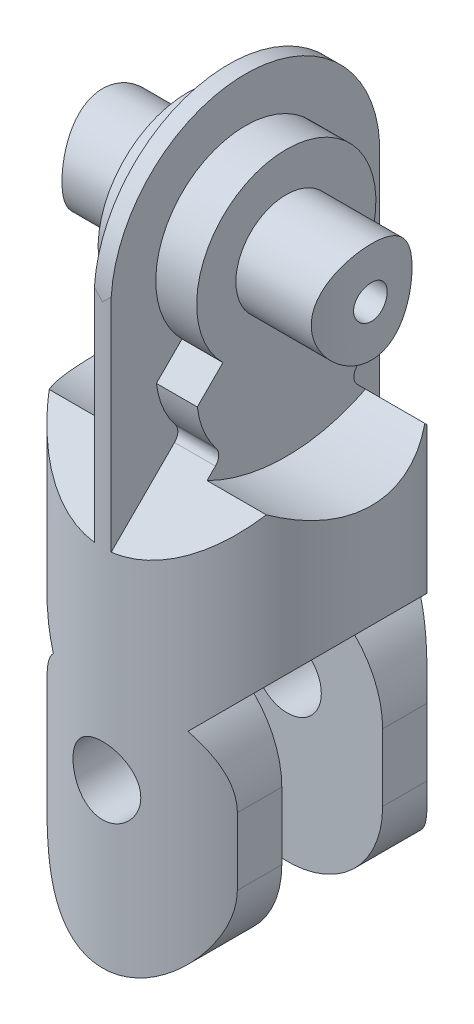
SolidWorks part; units mm, degrees
ref_plane "Front Plane" through (0, 0, 0) normal (0, 0, 1) x (1, 0, 0)
ref_plane "Top Plane" through (0, 0, 0) normal (0, 1, 0) x (1, 0, 0)
ref_plane "Right Plane" through (0, 0, 0) normal (1, 0, 0) x (0, 0, -1)
sketch "Sketch2" plane through (0, 0, 0) normal (0, 0, 1) x (1, 0, 0)
  line L0 (0, 31) -> (0, -14.8918) construction
  line L1 (0, 0) -> (-12, 0)
  line L2 (0, 0) -> (0, 31)
  line L3 (0, 31) -> (-12, 31)
  line L4 (-12, 0) -> (-12, 31)
  dimension "D1" = 24
  dimension "D2" = 31
revolve "Revolve1" add sketch "Sketch2" angle 360 about L0
sketch "Sketch1" plane through (0, 0, 0) normal (0, 0, 1) x (1, 0, 0)
  line L0 (-0.1796, 0.1796) -> (-12, 12)
  line L1 (-12, 12) -> (-12, -1)
  line L2 (-12, -1) -> (12, -1)
  line L3 (0, -1) -> (0, 0) construction
  line L4 (12, 12) -> (12, -1)
  line L5 (0.1796, 0.1796) -> (12, 12)
  line L7 (-12, 31) -> (-12, 0) construction
  arc A0 (0.1796, 0.1796) -> (-0.1796, 0.1796) centre (0, 0) ccw
  dimension "D1" = 90
  dimension "D2" = 0.254
  dimension "D3" = 1
extrude "Cut-Extrude1" cut sketch "Sketch1" against normal through all and the other way through all
sketch "Sketch3" plane through (0, 0, 0) normal (1, 0, 0) x (0, 0, -1)
  line L0 (-0.1796, 29.8204) -> (-12, 18)
  line L1 (-12, 31) -> (-12, 0.254) construction
  line L2 (-12, 18) -> (-12, 31)
  line L3 (-12, 31) -> (12, 31)
  line L4 (12, 31) -> (-12, 31) construction
  line L5 (0, 31) -> (0, 30) construction
  line L6 (12, 18) -> (12, 31)
  line L7 (0.1796, 29.8204) -> (12, 18)
  arc A0 (-0.1796, 29.8204) -> (0.1796, 29.8204) centre (0, 30) ccw
  dimension "D1" = 0.254
  dimension "D2" = 90
  dimension "D3" = 1
extrude "Cut-Extrude2" cut sketch "Sketch3" against normal through all and the other way through all
sketch "Sketch5" plane through (0, 0, 0) normal (0, 1, 0) x (1, 0, 0)
  line L0 (0, -4.45) -> (0, -17.835) construction
  line L1 (0, -4.45) -> (8, -4.45)
  line L2 (0, -4.45) -> (0, 4.45)
  line L3 (0, 4.45) -> (8, 4.45)
  line L4 (8, -4.45) -> (8, 4.45)
  dimension "D1" = 8
  dimension "D2" = 8.9
revolve "Revolve2" add sketch "Sketch5" angle 360 about L0
sketch "Sketch7" plane through (0, 0, 0) normal (0, 1, 0) x (1, 0, 0)
  line L0 (0, -19.45) -> (0, -4.2954) construction
  line L1 (0, -4.45) -> (9.25, -4.45)
  line L2 (0, -4.45) -> (0, -19.45)
  line L3 (0, -19.45) -> (9.25, -19.45)
  line L4 (9.25, -4.45) -> (9.25, -19.45)
  line L5 (-8, -4.45) -> (8, -4.45) construction
  dimension "D1" = 18.5
  dimension "D2" = 15
revolve "Cut-Revolve1" cut sketch "Sketch7" angle 360 about L0
sketch "Sketch8" plane through (0, 0, 0) normal (1, 0, 0) x (0, 0, -1)
  circle A0 centre (0, 30) radius 9.25
  dimension "D1" = 18.5
  dimension "D2" = 30
extrude "Cut-Extrude5" cut sketch "Sketch8" against normal through all from offset 4.4 offset against normal yes
mirror "Mirror1" about plane through (0, 0, 0) normal (1, 0, 0) of "Cut-Extrude5"
sketch "Sketch9" plane through (0, 0, 0) normal (1, 0, 0) x (0, 0, -1)
  circle A0 centre (0, 30) radius 8
  dimension "D1" = 16
extrude "Boss-Extrude1" add sketch "Sketch9" along normal up to surface and the other way up to surface up to face at (4.4, 25.9439, 0) other way up to face at (-4.4, 25.9439, 0)
mirror "Mirror2" about plane through (0, 0, 0) normal (0, 0, 1) of "Cut-Revolve1"
sketch "Sketch10" plane through (0, 0, 0) normal (1, 0, 0) x (0, 0, -1)
  circle A0 centre (0, 30) radius 1.95
  dimension "D1" = 3.9
extrude "Cut-Extrude6" cut sketch "Sketch10" against normal through all and the other way through all
sketch "Sketch11" plane through (0, 0, 0) normal (0, 0, 1) x (1, 0, 0)
  circle A0 centre (0, 0) radius 2.025
  dimension "D1" = 4.05
extrude "Cut-Extrude7" cut sketch "Sketch11" against normal through all and the other way through all
ref_plane "Plane1" through (0, 0, 7) normal (0, 0, 1) x (1, 0, 0)
ref_plane "Plane2" through (7, 0, 0) normal (1, 0, 0) x (0, 0, -1)
sketch "Sketch16" plane through (-4.4, 0, 0) normal (-1, 0, 0) x (0, 0, 1)
  line L0 (0, 30) -> (0, 37) construction
  line L1 (-8, 30) -> (-8, 37)
  line L2 (8, 30) -> (8, 37)
  arc A0 (-8, 30) -> (8, 30) centre (0, 30) ccw
  arc A1 (8, 37) -> (-8, 37) centre (0, 37) ccw
  arc A2 (5.6569, 24.3431) -> (-5.6569, 24.3431) centre (0, 30) ccw construction
  point P4 (0, 33.5)
  dimension "D1" = 7
extrude "Boss-Extrude2" add sketch "Sketch16" against normal up to surface (8.8 mm away)
sketch "Sketch17" plane through (-4.4, 0, 0) normal (-1, 0, 0) x (0, 0, 1)
  circle A0 centre (0, 37) radius 2.025
  dimension "D1" = 4.05
extrude "Cut-Extrude12" cut sketch "Sketch17" against normal through all
sketch "Sketch18" plane through (4.4, 0, 0) normal (1, 0, 0) x (0, 0, -1)
  line L0 (5.6569, 31.3431) -> (7.9441, 29.0559)
  line L1 (0, 37) -> (24.8471, 37) construction
  line L2 (8, 30) -> (8, 37) construction
  line L3 (8, 30) -> (8, 37)
  line L4 (0, 37) -> (0, 30) construction
  line L5 (-8, 30) -> (-8, 37)
  line L6 (-5.6569, 31.3431) -> (-7.9441, 29.0559)
  arc A0 (-5.6569, 31.3431) -> (-8, 37) centre (0, 37) cw
  arc A1 (5.6569, 24.3431) -> (8, 30) centre (0, 30) ccw construction
  arc A2 (7.9441, 29.0559) -> (8, 30) centre (0, 30) ccw
  arc A3 (5.6569, 31.3431) -> (8, 37) centre (0, 37) ccw
  arc A4 (-7.9441, 29.0559) -> (-8, 30) centre (0, 30) cw
  dimension "D1" = 45
extrude "Cut-Extrude13" cut sketch "Sketch18" against normal through all
sketch "Sketch19" plane through (0, 0, 0) normal (0, 0, 1) x (1, 0, 0)
  circle A0 centre (0, 0) radius 9.25
extrude "Cut-Extrude14" cut sketch "Sketch19" against normal through all and the other way through all
fillet "Fillet7" radius 1 2 edges at (0, 24.3431, 5.6569) (0, 24.3431, -5.6569)
sketch "Sketch20" plane through (0, 0, 0) normal (1, 0, 0) x (0, 0, -1)
  line L0 (-6.5407, 23.4593) -> (-12, 18) construction
  line L1 (0, 30) -> (-12, 18)
  line L2 (-12, 18) -> (-12, 37)
  line L3 (0, 37) -> (0, 19.0819) construction
  line L4 (12, 18) -> (12, 37)
  line L5 (0, 30) -> (12, 18)
  arc A0 (12, 37) -> (-12, 37) centre (0, 37) ccw
  circle A2 centre (0, 37) radius 2.025 construction
  circle A3 centre (0, 37) radius 2.025
extrude "Boss-Extrude3" add sketch "Sketch20" along normal blind 0.75 and the other way blind 0.75
sketch "Sketch21" plane through (0, 0, 0) normal (0, 0, 1) x (1, 0, 0)
  line L0 (0, 0) -> (0, -6) construction
  line L1 (8.5, 0) -> (8.5, -6)
  line L2 (-8.5, 0) -> (-8.5, -6)
  line L3 (6.5407, 6.5407) -> (12, 12) construction
  line L4 (-12, 12) -> (-6.5407, 6.5407) construction
  line L5 (6.0104, 6.0104) -> (6.5407, 6.5407)
  line L6 (-6.5407, 6.5407) -> (-6.0104, 6.0104)
  arc A1 (8.5, 0) -> (6.0104, 6.0104) centre (0, 0) ccw
  arc A2 (-8.5, -6) -> (8.5, -6) centre (0, -6) ccw
  circle A4 centre (0, 0) radius 2.025
  arc A5 (6.5407, 6.5407) -> (-6.5407, 6.5407) centre (0, 0) ccw construction
  arc A6 (6.5407, 6.5407) -> (-6.5407, 6.5407) centre (0, 0) ccw
  arc A7 (-6.0104, 6.0104) -> (-8.5, 0) centre (0, 0) ccw
  point P2 (0, -3)
  dimension "D2" = 4.05
  dimension "D3" = 8.5
  dimension "D4" = 8.5
  dimension "D1" = 6
  dimension "D5" = 8.5
extrude "Boss-Extrude4" add sketch "Sketch21" along normal blind 15 and the other way blind 15
sketch "Sketch23" plane through (0, 0, 0) normal (0, 0, 1) x (1, 0, 0)
  line L0 (0, 0) -> (0, -6) construction
  line L1 (9, 0) -> (9, -6)
  line L2 (-9, 0) -> (-9, -6)
  arc A0 (9, 0) -> (-9, 0) centre (0, 0) ccw
  arc A1 (-9, -6) -> (9, -6) centre (0, -6) ccw
  point P4 (0, -3)
  dimension "D1" = 9
extrude "Cut-Extrude16" cut sketch "Sketch23" against normal blind 4.5 and the other way blind 4.5
ref_plane "Plane3" through (0, 6, 0) normal (0, 1, 0) x (1, 0, 0)
sketch "Sketch26" [suppressed] plane through (0.75, 0, 0) normal (1, 0, 0) x (0, 0, -1)
  line L0 (5.6569, 31.3431) -> (7.9441, 29.0559) construction
  line L1 (6.3246, 23.6754) -> (11.9765, 18.0235) construction
  line L2 (12, 18) -> (12, 46) construction
  line L3 (7.9441, 29.0559) -> (12, 25)
  line L4 (6.3246, 23.6754) -> (12, 18)
  line L5 (12, 18) -> (12, 25)
  line L6 (0, 0) -> (0, 15.5647) construction
  line L7 (-12, 18) -> (-12, 25)
  line L8 (-6.3246, 23.6754) -> (-12, 18)
  line L9 (-7.9441, 29.0559) -> (-12, 25)
  arc A0 (6.2504, 25.0067) -> (7.9441, 29.0559) centre (0, 30) ccw construction
  arc A1 (6.2504, 25.0067) -> (6.3246, 23.6754) centre (7.0317, 24.3826) ccw construction
  arc A2 (6.2504, 25.0067) -> (7.9441, 29.0559) centre (0, 30) ccw
  arc A3 (6.2504, 25.0067) -> (6.3246, 23.6754) centre (7.0317, 24.3826) ccw
  arc A4 (-6.2504, 25.0067) -> (-6.3246, 23.6754) centre (-7.0317, 24.3826) cw
  arc A5 (-6.2504, 25.0067) -> (-7.9441, 29.0559) centre (0, 30) cw
extrude "Boss-Extrude5" [suppressed] add sketch "Sketch26" along normal up to surface (3.65 mm away)
sketch "Sketch27" [suppressed] plane through (-0.75, 0, 0) normal (-1, 0, 0) x (0, 0, 1)
  line L0 (0, 0) -> (0, 23.8803) construction
  line L1 (5.6569, 31.3431) -> (7.9441, 29.0559) construction
  line L2 (11.9765, 18.0235) -> (6.3246, 23.6754) construction
  line L3 (12, 46) -> (12, 18) construction
  line L4 (7.9441, 29.0559) -> (12, 25)
  line L5 (12, 18) -> (6.3246, 23.6754)
  line L6 (12, 25) -> (12, 18)
  line L7 (-12, 25) -> (-12, 18)
  line L8 (-12, 18) -> (-6.3246, 23.6754)
  line L9 (-7.9441, 29.0559) -> (-12, 25)
  arc A0 (6.2504, 25.0067) -> (7.9441, 29.0559) centre (0, 30) ccw construction
  arc A1 (6.2504, 25.0067) -> (6.3246, 23.6754) centre (7.0317, 24.3826) ccw construction
  arc A2 (6.2504, 25.0067) -> (7.9441, 29.0559) centre (0, 30) ccw
  arc A3 (6.2504, 25.0067) -> (6.3246, 23.6754) centre (7.0317, 24.3826) ccw
  arc A4 (-6.2504, 25.0067) -> (-6.3246, 23.6754) centre (-7.0317, 24.3826) cw
  arc A5 (-6.2504, 25.0067) -> (-7.9441, 29.0559) centre (0, 30) cw
extrude "Boss-Extrude6" [suppressed] add sketch "Sketch27" along normal up to surface (3.65 mm away)
ref_plane "Plane4" through (0, -6, 0) normal (0, 1, 0) x (1, 0, 0)
sketch "Sketch32" plane through (4.4, 0, 0) normal (1, 0, 0) x (0, 0, -1)
  circle A0 centre (0, 37) radius 15.75
  dimension "D1" = 31.5
extrude "Cut-Extrude19" cut sketch "Sketch32" along normal blind 10
sketch "Sketch33" plane through (4.4, 0, 0) normal (1, 0, 0) x (0, 0, -1)
  arc A0 (-4.4538, 21.8929) -> (4.4538, 21.8929) centre (0, 30) ccw construction
  arc A1 (4.4538, 21.8929) -> (7.0727, 22.9273) centre (0, 37) ccw construction
  arc A2 (-4.4538, 21.8929) -> (4.4538, 21.8929) centre (0, 30) ccw
  arc A3 (-4.4538, 21.8929) -> (4.4538, 21.8929) centre (0, 37) ccw
extrude "Boss-Extrude7" add sketch "Sketch33" along normal blind 10
mirror "Mirror8" about plane through (0, 0, 0) normal (1, 0, 0) of "Boss-Extrude7", "Cut-Extrude19"
sketch "Sketch34" plane through (0, 0, 0) normal (1, 0, 0) x (0, 0, -1)
  circle A0 centre (0, 37) radius 4.5
  circle A1 centre (0, 37) radius 1.5
  dimension "D1" = 9
  dimension "D2" = 3
extrude "Boss-Extrude8" add sketch "Sketch34" along normal blind 15 and the other way blind 15
sketch "Sketch35" plane through (0, 0, 0) normal (0, 0, 1) x (1, 0, 0)
  circle A0 centre (0, 0) radius 3.025
  dimension "D1" = 6.05
extrude "Cut-Extrude20" cut sketch "Sketch35" against normal through all and the other way through all
sketch "Sketch22" plane through (0, 0, 0) normal (0, 1, 0) x (1, 0, 0)
  circle A0 centre (0, 0) radius 12
  circle A1 centre (0, 0) radius 25
  dimension "D1" = 24
  dimension "D2" = 50
extrude "Cut-Extrude15" cut sketch "Sketch22" against normal through all and the other way through all
scale "Scale1" scale about centroid uniform scaling yes scale factor 0.333333
ref_axis "Axis1" through (-11.8715, 22.4638, 0) along (1, 0, 0)
ref_axis "Axis2" through (0, 10.1305, -45.9039) along (0, 0, 1)
